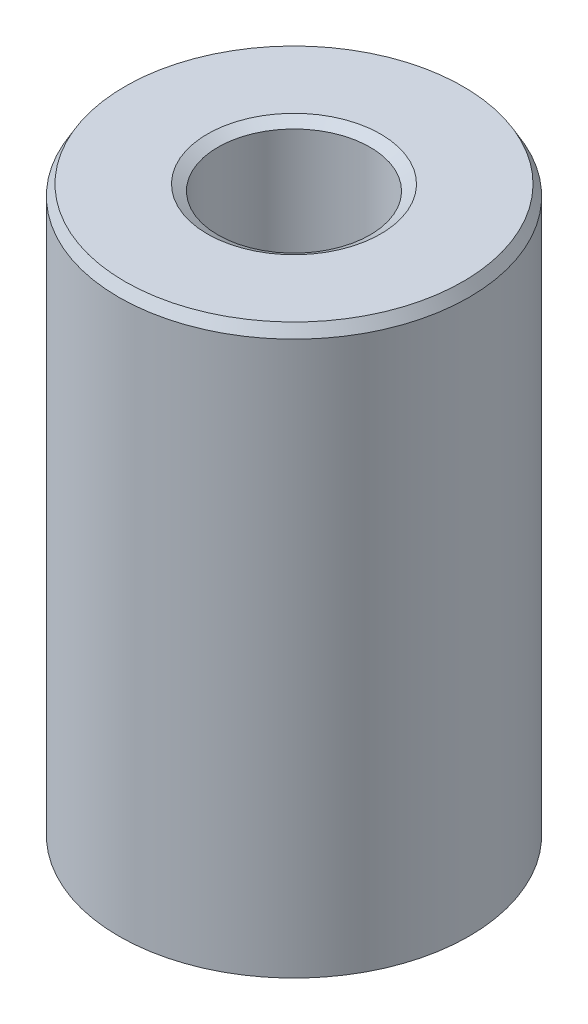
SolidWorks part; units mm, degrees
ref_plane "Front Plane" through (0, 0, 0) normal (0, 0, 1) x (1, 0, 0)
ref_plane "Top Plane" through (0, 0, 0) normal (0, 1, 0) x (1, 0, 0)
ref_plane "Right Plane" through (0, 0, 0) normal (1, 0, 0) x (0, 0, -1)
sketch "Sketch1" plane through (0, 0, 0) normal (0, 1, 0) x (1, 0, 0)
  circle A0 centre (0, 0) radius 55
  dimension "SLEEVE_OD" = 110
extrude "Boss-Extrude1" add sketch "Sketch1" along normal blind 178.9979
sketch "Sketch2" plane through (0, 0, 0) normal (0, 1, 0) x (1, 0, 0)
  circle A0 centre (0, 0) radius 23.8896
  dimension "BORE_D" = 47.7793
extrude "Cut-Extrude1" cut sketch "Sketch2" along normal through all
chamfer "Chamfer1" distance 3.3184 angle 30 4 edges at (0, 178.9979, 23.8896) (0, 0, 23.8896) (0, 0, 55) (0, 178.9979, 55) first distance on face at (0, 178.9979, 23.8896) first distance on face at (0, 0, 23.8896) first distance on face at (0, 178.9979, 55)
